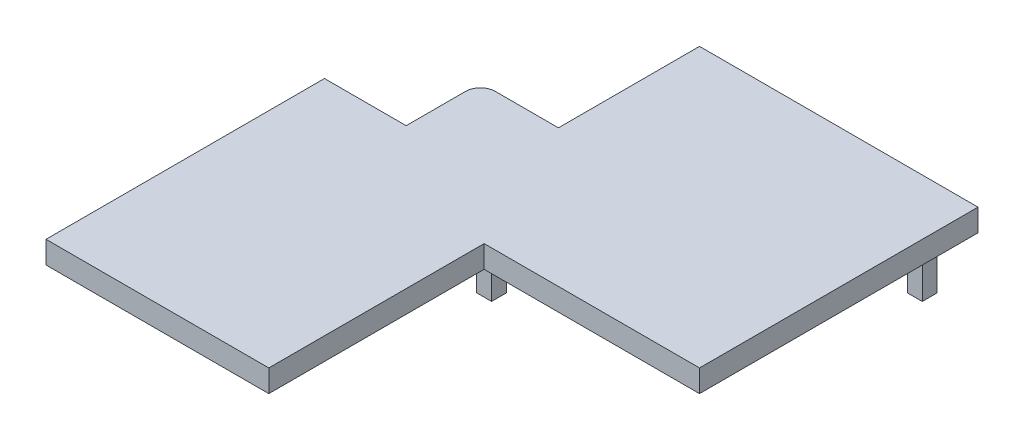
SolidWorks part; units mm, degrees
ref_plane "Front Plane" through (0, 0, 0) normal (0, 0, 1) x (1, 0, 0)
ref_plane "Top Plane" through (0, 0, 0) normal (0, 1, 0) x (1, 0, 0)
ref_plane "Right Plane" through (0, 0, 0) normal (1, 0, 0) x (0, 0, -1)
sketch "Sketch1" plane through (0, 0, 0) normal (0, 1, 0) x (1, 0, 0)
  line L0 (75.4598, -9.7354) -> (75.4598, 85.5146)
  line L1 (75.4598, 85.5146) -> (-19.7902, 85.5146)
  line L2 (-19.7902, 85.5146) -> (-19.7902, 11.8546)
  line L3 (-19.7902, 11.8546) -> (-74.4002, 11.8546)
  line L4 (-74.4002, 11.8546) -> (-74.4002, -83.3954)
  line L5 (-74.4002, -83.3954) -> (1.7998, -83.3954)
  line L6 (1.7998, -83.3954) -> (1.7998, -9.7354)
  line L7 (1.7998, -9.7354) -> (75.4598, -9.7354)
  line L8 (19.5798, 21.3796) -> (18.3098, 21.3796)
  line L9 (18.3098, 34.0796) -> (19.5798, 34.0796)
  line L10 (18.3098, 21.3796) -> (18.3098, 34.0796)
  line L11 (19.5798, 34.0796) -> (19.5798, 21.3796)
  line L12 (24.0248, 34.0796) -> (25.2948, 34.0796)
  line L13 (25.2948, 21.3796) -> (24.0248, 21.3796)
  line L14 (25.2948, 34.0796) -> (25.2948, 21.3796)
  line L15 (24.0248, 21.3796) -> (24.0248, 34.0796)
  line L16 (29.7398, 34.0796) -> (31.0098, 34.0796)
  line L17 (29.7398, 21.3796) -> (29.7398, 34.0796)
  line L18 (31.0098, 34.0796) -> (31.0098, 21.3796)
  line L19 (31.0098, 21.3796) -> (29.7398, 21.3796)
  line L20 (44.9798, 21.3796) -> (43.7098, 21.3796)
  line L21 (43.7098, 21.3796) -> (43.7098, 34.0796)
  line L22 (44.9798, 34.0796) -> (44.9798, 21.3796)
  line L23 (43.7098, 34.0796) -> (44.9798, 34.0796)
  line L24 (49.4248, 34.0796) -> (50.6948, 34.0796)
  line L25 (49.4248, 21.3796) -> (49.4248, 34.0796)
  line L26 (50.6948, 34.0796) -> (50.6948, 21.3796)
  line L27 (50.6948, 21.3796) -> (49.4248, 21.3796)
  line L28 (56.4098, 21.3796) -> (55.1398, 21.3796)
  line L29 (55.1398, 34.0796) -> (56.4098, 34.0796)
  line L30 (55.1398, 21.3796) -> (55.1398, 34.0796)
  line L31 (56.4098, 34.0796) -> (56.4098, 21.3796)
  line L44 (-36.3002, -55.4554) -> (-37.5702, -55.4554)
  line L45 (-37.5702, -55.4554) -> (-37.5702, -42.7554)
  line L46 (-37.5702, -42.7554) -> (-36.3002, -42.7554)
  line L47 (-36.3002, -42.7554) -> (-36.3002, -55.4554)
  line L48 (-31.8552, -42.7554) -> (-30.5852, -42.7554)
  line L49 (-31.8552, -55.4554) -> (-31.8552, -42.7554)
  line L50 (-30.5852, -55.4554) -> (-31.8552, -55.4554)
  line L51 (-30.5852, -42.7554) -> (-30.5852, -55.4554)
  line L52 (-30.5852, -41.271) -> (-31.8552, -41.271)
  line L53 (-30.5852, -28.571) -> (-30.5852, -41.271)
  line L54 (-31.8552, -41.271) -> (-31.8552, -28.571)
  line L55 (-31.8552, -28.571) -> (-30.5852, -28.571)
  line L56 (-37.5702, -28.571) -> (-36.3002, -28.571)
  line L57 (-36.3002, -28.571) -> (-36.3002, -41.271)
  line L58 (-37.5702, -41.271) -> (-37.5702, -28.571)
  line L59 (-36.3002, -41.271) -> (-37.5702, -41.271)
  line L60 (-43.2852, -28.571) -> (-42.0152, -28.571)
  line L61 (-42.0152, -28.571) -> (-42.0152, -41.271)
  line L62 (-43.2852, -41.271) -> (-43.2852, -28.571)
  line L63 (-42.0152, -41.271) -> (-43.2852, -41.271)
  line L64 (-43.2852, -42.7554) -> (-42.0152, -42.7554)
  line L65 (-43.2852, -55.4554) -> (-43.2852, -42.7554)
  line L66 (-42.0152, -55.4554) -> (-43.2852, -55.4554)
  line L67 (-42.0152, -42.7554) -> (-42.0152, -55.4554)
  line L68 (-30.5852, -55.4554) -> (-30.5852, 11.8546)
  line L71 (-43.2852, -55.4554) -> (-30.5852, -55.4554)
  line L73 (18.3098, 21.3796) -> (56.4098, 21.3796)
  line L74 (18.3098, 21.3796) -> (18.3098, 34.0796)
  line L75 (18.3098, 34.0796) -> (56.4098, 34.0796)
  line L76 (56.4098, 21.3796) -> (56.4098, 34.0796)
  line L77 (-30.5852, 11.8546) -> (-43.2852, 11.8546)
  line L78 (-43.2852, 11.8546) -> (-43.2852, -55.4554)
  line L79 (18.3098, 34.0796) -> (-19.7902, 34.0796)
  line L80 (18.3098, 21.3796) -> (-19.7902, 21.3796)
  line L81 (-5.1852, -0.2104) -> (-5.1852, 4.8696)
  line L82 (-5.1852, 4.8696) -> (-10.2652, 4.8696)
  line L83 (-10.2652, 4.8696) -> (-10.2652, -0.2104)
  line L84 (-10.2652, -0.2104) -> (-5.1852, -0.2104)
  line L85 (-5.1852, 78.5296) -> (-10.2652, 78.5296)
  line L86 (-10.2652, 78.5296) -> (-10.2652, 73.4496)
  line L87 (-10.2652, 73.4496) -> (-5.1852, 73.4496)
  line L88 (-5.1852, 73.4496) -> (-5.1852, 78.5296)
  line L89 (68.483, 73.4333) -> (68.483, 78.5133)
  line L90 (68.483, 78.5133) -> (63.403, 78.5133)
  line L91 (63.403, 78.5133) -> (63.403, 73.4333)
  line L92 (63.403, 73.4333) -> (68.483, 73.4333)
extrude "Boss-Extrude2" add sketch "Sketch1" against normal blind 5.08 contours L6 L7 L0 L1 L2 L3 L4 L5 L53 L51 L50 L71 L44 L66 L65 L62 L60 L56 L55 L9 L75 L12 L16 L23 L24 region at (0.416, 0, -5.1171)
sketch "Sketch4" plane through (0, 0, 0) normal (0, 1, 0) x (1, 0, 0)
  line L0 (-19.7902, 85.5146) -> (-19.7902, 34.0796) construction
  line L1 (-19.7902, 11.8546) -> (-46.4602, 11.8546)
  line L2 (-19.7902, 11.8546) -> (-19.7902, 37.2546)
  line L3 (-19.7902, 37.2546) -> (-46.4602, 37.2546)
  line L4 (-46.4602, 11.8546) -> (-46.4602, 37.2546)
  line L5 (-19.7902, 11.8546) -> (-30.5852, 11.8546) construction
  line L6 (-19.7902, 34.0796) -> (-43.2852, 34.0796)
  line L7 (-43.2852, 34.0796) -> (-43.2852, 11.8546)
  line M6 (-19.7902, 85.5146) -> (-19.7902, 34.0796)
  line M7 (-19.7902, 11.8546) -> (-30.5852, 11.8546)
  line M24 (-19.7902, 21.3796) -> (-19.7902, 11.8546)
  dimension "D1" = 25.4
  dimension "D2" = 26.67
extrude "Boss-Extrude7" add sketch "Sketch4" against normal blind 5.08 contours L7 L6 L3 L4 L1 M6 region at (-44.8727, 0, -12.2229)
extrude "Boss-Extrude8" add sketch "Sketch4<5>" against normal blind 1.27 separate body contours L6 L7 L1 L2 M7 M24 region at (-31.5377, 0, -22.9671)
sketch "Sketch4<5>" plane through (0, 0, 0) normal (0, 1, 0) x (1, 0, 0) same geometry as "Sketch4"
sketch "Sketch5" plane through (-30.5852, 0, 0) normal (-1, 0, 0) x (0, 0, 1)
  line L0 (55.4554, -5.08) -> (55.4554, 0)
  line L1 (55.4554, 0) -> (-11.8546, 0)
  line L2 (-11.8546, 0) -> (-11.8546, -1.2797)
  line L3 (-11.8546, -5.08) -> (-11.8546, 0) construction
  line L4 (-11.8546, -1.2797) -> (55.4554, -5.08)
extrude "Boss-Extrude9" add sketch "Sketch5" along normal blind 12.7
sketch "Sketch6" plane through (0, 0, -34.0796) normal (0, 0, 1) x (1, 0, 0)
  line L0 (56.4098, -5.08) -> (56.4098, 0)
  line L1 (56.4098, 0) -> (-19.7902, 0)
  line L2 (-19.7902, 0) -> (-19.7902, -1.27)
  line L3 (-19.7902, -1.27) -> (56.4098, -5.08)
extrude "Boss-Extrude10" add sketch "Sketch6" along normal blind 12.7
extrude "Boss-Extrude12" add sketch "Sketch1<5>" against normal blind 25.4 contours L87 L88 L85 L86 | L91 L92 L89 L90 | L83 L84 L81 L82 region at (-7.7252, 0, -2.3296) region at (-7.7252, 0, -75.9896) region at (65.943, 0, -75.9733)
sketch "Sketch1<5>" plane through (0, 0, 0) normal (0, 1, 0) x (1, 0, 0) same geometry as "Sketch1"
sketch "Sketch7" plane through (0, -5.08, 0) normal (0, -1, 0) x (1, 0, 0)
  line L0 (-30.5852, 55.4554) -> (-43.2852, 55.4554) construction
  line L1 (-19.7902, -21.3796) -> (-19.7902, -11.8546) construction
  line L2 (-19.7902, -11.8546) -> (-30.5852, -11.8546) construction
  line L3 (-30.5852, -11.8546) -> (-30.5852, 55.4554) construction
  line L4 (-43.2852, 55.4554) -> (-43.2852, -34.0796) construction
  line L5 (56.4098, -34.0796) -> (-43.2852, -34.0796) construction
  line L6 (56.4098, -34.0796) -> (56.4098, -21.3796) construction
  line L7 (-19.7902, -21.3796) -> (56.4098, -21.3796) construction
  line L8 (-30.5852, 55.4554) -> (-43.2852, 55.4554)
  line L9 (-19.7902, -21.3796) -> (-19.7902, -11.8546)
  line L10 (-74.4002, -11.8546) -> (-46.4602, -11.8546)
  line L11 (-46.4602, -11.8546) -> (-46.4602, -37.2546)
  line L12 (-46.4602, -37.2546) -> (-19.7902, -37.2546)
  line L13 (-19.7902, -37.2546) -> (-19.7902, -85.5146)
  line L14 (-19.7902, -85.5146) -> (75.4598, -85.5146)
  line L15 (75.4598, -85.5146) -> (75.4598, 9.7354)
  line L16 (75.4598, 9.7354) -> (1.7998, 9.7354)
  line L17 (1.7998, 9.7354) -> (1.7998, 83.3954)
  line L18 (1.7998, 83.3954) -> (-74.4002, 83.3954)
  line L19 (-74.4002, 83.3954) -> (-74.4002, -11.8546)
  line L20 (-74.4002, -11.8546) -> (-46.4602, -11.8546)
  line L21 (-46.4602, -11.8546) -> (-46.4602, -37.2546)
  line L22 (-46.4602, -37.2546) -> (-19.7902, -37.2546)
  line L23 (-19.7902, -37.2546) -> (-19.7902, -85.5146)
  line L24 (-19.7902, -85.5146) -> (75.4598, -85.5146)
  line L25 (75.4598, -85.5146) -> (75.4598, 9.7354)
  line L26 (75.4598, 9.7354) -> (1.7998, 9.7354)
  line L27 (1.7998, 9.7354) -> (1.7998, 83.3954)
  line L28 (1.7998, 83.3954) -> (-74.4002, 83.3954)
  line L29 (-74.4002, 83.3954) -> (-74.4002, -11.8546)
  line L30 (-19.7902, -11.8546) -> (-30.5852, -11.8546)
  line L31 (-30.5852, -11.8546) -> (-30.5852, 55.4554)
  line L32 (-43.2852, 55.4554) -> (-43.2852, -34.0796)
  line L33 (56.4098, -34.0796) -> (-43.2852, -34.0796)
  line L34 (56.4098, -34.0796) -> (56.4098, -21.3796)
  line L35 (-19.7902, -21.3796) -> (56.4098, -21.3796)
  dimension "D1" = 0
extrude "Boss-Extrude13" add sketch "Sketch7" along normal blind 2.54
fillet "Fillet4" radius 5.08 3 edges at (-19.7902, -4.445, -11.8546) (-43.2852, -4.445, -34.0796) (-46.4602, -3.81, -37.2546)
